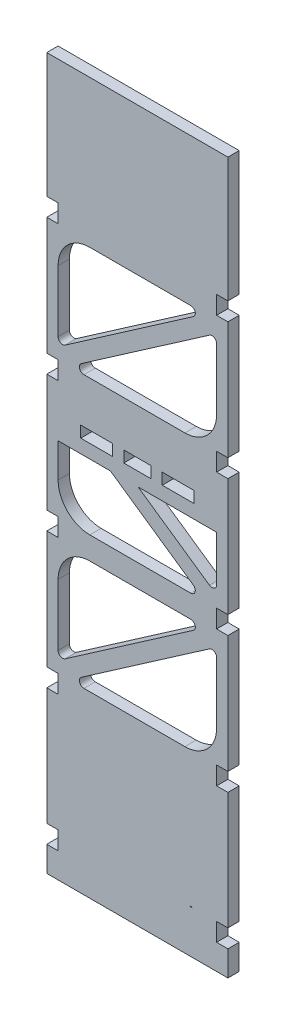
SolidWorks part; units mm, degrees
material "Balsa"
ref_plane "Front Plane" through (0, 0, 0) normal (0, 0, 1) x (1, 0, 0)
ref_plane "Top Plane" through (0, 0, 0) normal (0, 1, 0) x (1, 0, 0)
ref_plane "Right Plane" through (0, 0, 0) normal (1, 0, 0) x (0, 0, -1)
sketch "Model" plane through (0, 0, 0) normal (0, 0, 1) x (1, 0, 0)
  line L0 (77.47, 87.63) -> (20.8312, 87.63)
  line L1 (95.25, 35.3278) -> (95.25, 69.85)
  line L2 (19.3854, 83.0016) -> (91.2642, 33.2394)
  line L3 (6.35, 146.05) -> (6.35, 111.5278)
  line L4 (80.7688, 163.83) -> (24.13, 163.83)
  line L5 (10.3358, 109.4394) -> (82.2146, 159.2016)
  line L6 (77.47, 240.03) -> (20.8312, 240.03)
  line L7 (95.25, 187.7278) -> (95.25, 222.25)
  line L8 (19.3854, 235.4016) -> (91.2642, 185.6394)
  line L9 (24.13, 176.53) -> (80.7688, 176.53)
  line L10 (6.35, 228.8322) -> (6.35, 194.31)
  line L11 (82.2146, 181.1584) -> (10.3358, 230.9206)
  line L12 (91.2642, 154.7206) -> (19.3854, 104.9584)
  line L13 (95.25, 118.11) -> (95.25, 152.6322)
  line L14 (20.8312, 100.33) -> (77.47, 100.33)
  line L15 (6.35, 298.45) -> (6.35, 263.9278)
  line L16 (80.7688, 316.23) -> (24.13, 316.23)
  line L17 (10.3358, 261.8394) -> (82.2146, 311.6016)
  line L18 (88.9, 392.43) -> (20.8312, 392.43)
  line L19 (95.25, 340.1278) -> (95.25, 386.08)
  line L20 (19.3854, 387.8016) -> (91.2642, 338.0394)
  line L21 (24.13, 328.93) -> (80.7688, 328.93)
  line L22 (6.35, 381.2322) -> (6.35, 346.71)
  line L23 (82.2146, 333.5584) -> (10.3358, 383.3206)
  line L24 (24.13, 24.3357) -> (79.7674, 24.3357)
  line L25 (6.35, 76.4322) -> (6.35, 42.1157)
  line L26 (81.3163, 29.1503) -> (9.4375, 78.9125)
  line L27 (91.2642, 307.1206) -> (19.3854, 257.3584)
  line L28 (95.25, 270.51) -> (95.25, 305.0322)
  line L29 (20.8312, 252.73) -> (77.47, 252.73)
  line L30 (0, 398.78) -> (0, 0)
  line L31 (0, 0) -> (101.6, 0)
  line L32 (101.6, 398.78) -> (101.6, 0)
  line L33 (0, 398.78) -> (101.6, 398.78)
  arc A1 (91.2642, 33.2394) -> (95.25, 35.3278) centre (92.71, 35.3278) ccw
  arc A2 (20.8312, 87.63) -> (19.3854, 83.0016) centre (20.8312, 85.09) ccw
  arc A4 (82.2146, 159.2016) -> (80.7688, 163.83) centre (80.7688, 161.29) ccw
  arc A5 (6.35, 111.5278) -> (10.3358, 109.4394) centre (8.89, 111.5278) ccw
  arc A7 (91.2642, 185.6394) -> (95.25, 187.7278) centre (92.71, 187.7278) ccw
  arc A8 (20.8312, 240.03) -> (19.3854, 235.4016) centre (20.8312, 237.49) ccw
  arc A10 (10.3358, 230.9206) -> (6.35, 228.8322) centre (8.89, 228.8322) ccw
  arc A11 (80.7688, 176.53) -> (82.2146, 181.1584) centre (80.7688, 179.07) ccw
  arc A12 (95.25, 152.6322) -> (91.2642, 154.7206) centre (92.71, 152.6322) ccw
  arc A14 (19.3854, 104.9584) -> (20.8312, 100.33) centre (20.8312, 102.87) ccw
  arc A16 (82.2146, 311.6016) -> (80.7688, 316.23) centre (80.7688, 313.69) ccw
  arc A17 (6.35, 263.9278) -> (10.3358, 261.8394) centre (8.89, 263.9278) ccw
  arc A18 (95.25, 386.08) -> (88.9, 392.43) centre (88.9, 386.08) ccw
  arc A19 (91.2642, 338.0394) -> (95.25, 340.1278) centre (92.71, 340.1278) ccw
  arc A20 (20.8312, 392.43) -> (19.3854, 387.8016) centre (20.8312, 389.89) ccw
  arc A22 (10.3358, 383.3206) -> (6.35, 381.2322) centre (8.89, 381.2322) ccw
  arc A23 (80.7688, 328.93) -> (82.2146, 333.5584) centre (80.7688, 331.47) ccw
  arc A25 (9.4375, 78.9125) -> (6.35, 76.4322) centre (8.89, 76.4322) ccw
  arc A26 (79.7674, 24.3357) -> (81.3163, 29.1503) centre (80.7688, 26.67) ccw
  arc A27 (95.25, 305.0322) -> (91.2642, 307.1206) centre (92.71, 305.0322) ccw
  arc A29 (19.3854, 257.3584) -> (20.8312, 252.73) centre (20.8312, 255.27) ccw
  arc A30 (6.35, 42.1157) -> (24.13, 24.3357) centre (24.13, 42.1157) ccw
  arc A31 (6.35, 346.71) -> (24.13, 328.93) centre (24.13, 346.71) ccw
  arc A32 (6.35, 298.45) -> (24.13, 316.23) centre (24.13, 298.45) cw
  arc A33 (95.25, 270.51) -> (77.47, 252.73) centre (77.47, 270.51) cw
  arc A34 (77.47, 240.03) -> (95.25, 222.25) centre (77.47, 222.25) cw
  arc A35 (6.35, 194.31) -> (24.13, 176.53) centre (24.13, 194.31) ccw
  arc A36 (6.35, 146.05) -> (24.13, 163.83) centre (24.13, 146.05) cw
  arc A37 (77.47, 100.33) -> (95.25, 118.11) centre (77.47, 118.11) ccw
  arc A38 (77.47, 87.63) -> (95.25, 69.85) centre (77.47, 69.85) cw
  dimension "D3" = 6.35
  dimension "D4" = 2.54
  dimension "D5" = 2.54
  dimension "D6" = 2.54
  dimension "D7" = 2.54
  dimension "D8" = 2.54
  dimension "D9" = 2.54
  dimension "D10" = 2.54
  dimension "D11" = 2.54
  dimension "D12" = 2.54
  dimension "D13" = 2.54
  dimension "D14" = 2.54
  dimension "D15" = 2.54
  dimension "D16" = 2.54
  dimension "D17" = 2.54
  dimension "D18" = 2.54
  dimension "D19" = 2.54
  dimension "D20" = 2.54
  dimension "D21" = 2.54
  dimension "D22" = 2.54
  dimension "D26" = 17.78
  dimension "D27" = 17.78
  dimension "D1" = 398.78
  dimension "D2" = 101.6
  dimension "D23" = 26.67
  dimension "D24" = 20.8312
  dimension "D25" = 87.4233
extrude "Boss-Extrude1" add sketch "Model" along normal blind 6.35
sketch "Sketch1" plane through (0, 0, 6.35) normal (0, 0, 1) x (1, 0, 0)
  line L0 (101.6, 0) -> (101.6, 398.78) construction
  line L1 (101.6, 328.93) -> (95.25, 328.93)
  line L2 (101.6, 328.93) -> (101.6, 318.77)
  line L3 (101.6, 318.77) -> (95.25, 318.77)
  line L4 (95.25, 328.93) -> (95.25, 318.77)
  line L5 (0, 398.78) -> (0, 0) construction
  line L6 (0, 252.73) -> (6.35, 252.73)
  line L7 (0, 252.73) -> (0, 242.57)
  line L8 (0, 242.57) -> (6.35, 242.57)
  line L9 (6.35, 252.73) -> (6.35, 242.57)
  line L10 (24.13, 328.93) -> (80.7688, 328.93) construction
  line L11 (101.6, 176.53) -> (95.25, 176.53)
  line L12 (101.6, 176.53) -> (101.6, 166.37)
  line L13 (101.6, 166.37) -> (95.25, 166.37)
  line L14 (95.25, 176.53) -> (95.25, 166.37)
  line L15 (0, 100.33) -> (6.35, 100.33)
  line L16 (0, 100.33) -> (0, 90.17)
  line L17 (0, 90.17) -> (6.35, 90.17)
  line L18 (6.35, 100.33) -> (6.35, 90.17)
  line L19 (20.8312, 252.73) -> (77.47, 252.73) construction
  line L21 (20.8312, 100.33) -> (77.47, 100.33) construction
  line L22 (24.13, 24.3357) -> (79.7674, 24.3357) construction
  line L23 (0, 328.93) -> (6.35, 328.93)
  line L24 (0, 328.93) -> (0, 318.77)
  line L25 (0, 318.77) -> (6.35, 318.77)
  line L26 (6.35, 328.93) -> (6.35, 318.77)
  line L27 (101.6, 252.73) -> (95.25, 252.73)
  line L28 (101.6, 252.73) -> (101.6, 242.57)
  line L29 (101.6, 242.57) -> (95.25, 242.57)
  line L30 (95.25, 252.73) -> (95.25, 242.57)
  line L31 (0, 176.53) -> (6.35, 176.53)
  line L32 (0, 176.53) -> (0, 166.37)
  line L33 (0, 166.37) -> (6.35, 166.37)
  line L34 (6.35, 176.53) -> (6.35, 166.37)
  line L35 (101.6, 100.33) -> (95.25, 100.33)
  line L36 (101.6, 100.33) -> (101.6, 90.17)
  line L37 (101.6, 90.17) -> (95.25, 90.17)
  line L38 (95.25, 100.33) -> (95.25, 90.17)
  line L39 (0, 24.3357) -> (6.35, 24.3357)
  line L40 (0, 24.3357) -> (0, 14.1757)
  line L41 (0, 14.1757) -> (6.35, 14.1757)
  line L42 (6.35, 24.3357) -> (6.35, 14.1757)
  line L43 (101.6, 24.3357) -> (95.25, 24.3357)
  line L44 (101.6, 24.3357) -> (101.6, 14.1757)
  line L45 (101.6, 14.1757) -> (95.25, 14.1757)
  line L46 (95.25, 24.3357) -> (95.25, 14.1757)
  line L47 (24.13, 176.53) -> (80.7688, 176.53) construction
  dimension "D1" = 6.35
  dimension "D2" = 10.16
  dimension "D3" = 10.16
  dimension "D4" = 6.35
  dimension "D5" = 6.35
  dimension "D6" = 10.16
  dimension "D7" = 6.35
  dimension "D8" = 10.16
  dimension "D9" = 10.16
  dimension "D10" = 10.16
extrude "Cut-Extrude1" cut sketch "Sketch1" against normal up to surface (6.35 mm away) contours L1 L4 L3 L2 | L27 L30 L29 L28 | L9 L6 L7 L8 | L42 L39 L40 L41 | L11 L14 L13 L12 | L26 L25 L24 L23 | L43 L46 L45 L44 | L38 L37 L36 L35 | L15 L18 L17 L16 | L31 L34 L33 L32 region at (98.425, 323.85, 6.35) region at (3.175, 247.65, 6.35) region at (98.425, 171.45, 6.35) region at (98.425, 247.65, 6.35) region at (3.175, 19.2557, 6.35) up to face at (50.8, 199.39, 0)
sketch "Sketch3" plane through (0, 0, 6.35) normal (0, 0, 1) x (1, 0, 0)
  line L0 (101.6, 176.53) -> (101.6, 242.57) construction
  line L1 (101.6, 213.36) -> (0, 213.36)
  line L2 (101.6, 213.36) -> (101.6, 242.57)
  line L3 (101.6, 242.57) -> (0, 242.57)
  line L4 (0, 213.36) -> (0, 242.57)
  line L5 (24.13, 176.53) -> (80.7688, 176.53) construction
  line L7 (6.35, 90.17) -> (95.25, 90.17)
  line L8 (6.35, 90.17) -> (6.35, 24.3357)
  line L9 (6.35, 24.3357) -> (95.25, 24.3357)
  line L10 (95.25, 90.17) -> (95.25, 24.3357)
  line L11 (6.35, 328.93) -> (101.6, 328.93)
  line L12 (6.35, 328.93) -> (6.35, 398.78)
  line L13 (6.35, 398.78) -> (101.6, 398.78)
  line L14 (101.6, 328.93) -> (101.6, 398.78)
  dimension "D1" = 36.83
extrude "Boss-Extrude2" add sketch "Sketch3" against normal up to surface (6.35 mm away) up to face at (50.8, 174.0274, 0)
sketch "Sketch4" plane through (0, 0, 6.35) normal (0, 0, 1) x (1, 0, 0)
  line L0 (6.35, 213.36) -> (35.7011, 213.36) construction
  line L1 (82.55, 220.98) -> (64.77, 220.98)
  line L2 (82.55, 220.98) -> (82.55, 227.33)
  line L3 (82.55, 227.33) -> (64.77, 227.33)
  line L4 (64.77, 220.98) -> (64.77, 227.33)
  line L5 (58.42, 220.98) -> (43.18, 220.98)
  line L6 (58.42, 220.98) -> (58.42, 227.33)
  line L7 (58.42, 227.33) -> (43.18, 227.33)
  line L8 (43.18, 220.98) -> (43.18, 227.33)
  line L9 (36.83, 220.98) -> (19.05, 220.98)
  line L10 (36.83, 220.98) -> (36.83, 227.33)
  line L11 (36.83, 227.33) -> (19.05, 227.33)
  line L12 (19.05, 220.98) -> (19.05, 227.33)
  line L13 (0, 242.57) -> (0, 176.53) construction
  point P14 (36.83, 224.155)
  dimension "D1" = 6.35
  dimension "D2" = 7.62
  dimension "D3" = 17.78
  dimension "D4" = 15.24
  dimension "D5" = 17.78
  dimension "D6" = 6.35
  dimension "D7" = 6.35
  dimension "D8" = 19.05
extrude "Cut-Extrude2" cut sketch "Sketch4" against normal up to surface (6.35 mm away) up to face at (80.7688, 24.2329, 0)
equation "\"thick\"=0.25"
equation "\"D1@Boss-Extrude1\"=\"thick\""
